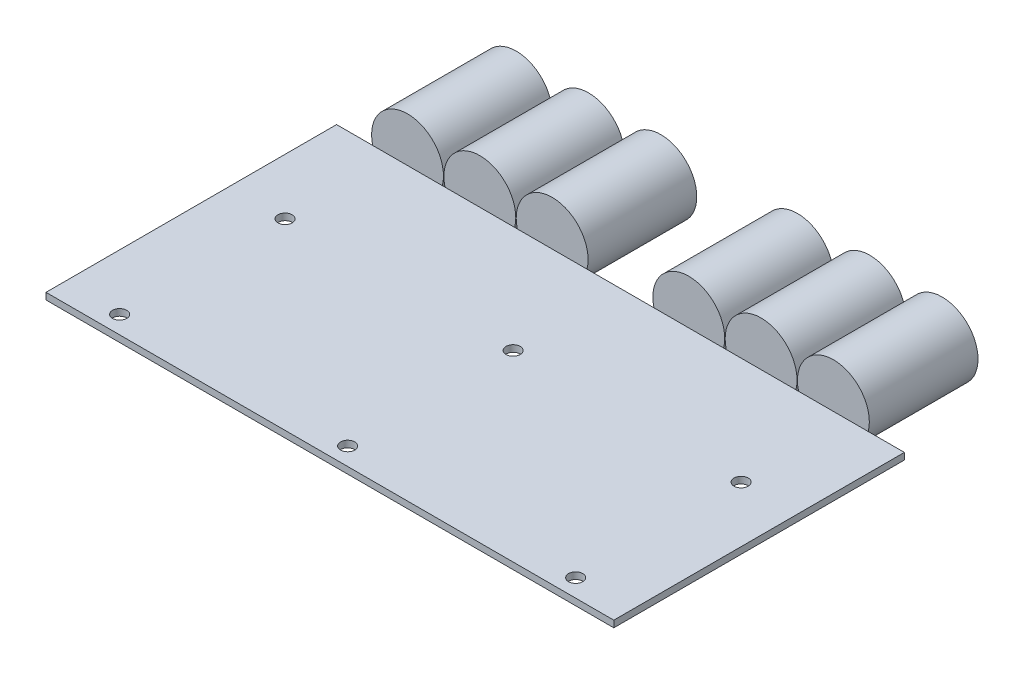
SolidWorks part; units mm, degrees
ref_plane "Front Plane" through (0, 0, 0) normal (0, 0, 1) x (1, 0, 0)
ref_plane "Top Plane" through (0, 0, 0) normal (0, 1, 0) x (1, 0, 0)
ref_plane "Right Plane" through (0, 0, 0) normal (1, 0, 0) x (0, 0, -1)
sketch "Sketch1" plane through (0, 0, 0) normal (0, 1, 0) x (1, 0, 0)
  line L1 (64, 32.75) -> (-64, 32.75)
  line L2 (64, 32.75) -> (64, -32.75)
  line L3 (64, -32.75) -> (-64, -32.75)
  line L4 (-64, 32.75) -> (-64, -32.75)
  line L5 (64, 32.75) -> (-64, -32.75) construction
  line L6 (64, -32.75) -> (-64, 32.75) construction
  point P0 (0, 0)
  dimension "D1" = 65.5
  dimension "D2" = 128
extrude "Boss-Extrude1" add sketch "Sketch1" along normal blind 1.5
sketch "Sketch2" plane through (0, 0, 0) normal (0, 1, 0) x (1, 0, 0)
  line L0 (0, 8.55) -> (0, -28.75) construction
  line L2 (-64, -32.75) -> (64, -32.75) construction
  line L3 (-64, 32.75) -> (-64, -32.75) construction
  circle A0 centre (-51.4, -28.75) radius 1.6
  circle A1 centre (0, -28.75) radius 1.6
  circle A2 centre (51.4, -28.75) radius 1.6
  circle A3 centre (-51.4, 8.55) radius 1.6
  circle A4 centre (0, 8.55) radius 1.6
  circle A5 centre (51.4, 8.55) radius 1.6
  point P12 (0, 0)
  point P13 (0, 9.9256)
  point P14 (0, 0)
  point P15 (0, -26.9408)
  point P16 (0, 0)
  point P17 (-0.5672, 8.0822)
  dimension "D1" = 3.2
  dimension "D2" = 2.4
  dimension "D4" = 48.2
  dimension "D5" = 34.1
  dimension "D3" = 11
extrude "Cut-Extrude2" cut sketch "Sketch2" along normal through all
sketch "Sketch3" plane through (0, 0, 0) normal (0, -1, 0) x (1, 0, 0)
  line L0 (-64, 32.75) -> (64, 32.75) construction
  line L1 (52.5, 1.75) -> (-52.5, 1.75)
  line L2 (52.5, 1.75) -> (52.5, 19.75)
  line L3 (52.5, 19.75) -> (-52.5, 19.75)
  line L4 (-52.5, 1.75) -> (-52.5, 19.75)
  line L5 (52.5, 1.75) -> (-52.5, 19.75) construction
  line L6 (52.5, 19.75) -> (-52.5, 1.75) construction
  point P0 (0, 10.75)
  point P5 (0, 0)
  dimension "D1" = 105
  dimension "D2" = 18
  dimension "D3" = 13
extrude "Boss-Extrude2" add sketch "Sketch3" along normal blind 1
sketch "Sketch4" plane through (0, 0, -32.75) normal (0, 0, -1) x (-1, 0, 0)
  line L0 (0, 0) -> (0, 1.5) construction
  line L1 (-64, 1.5) -> (64, 1.5) construction
  circle A0 centre (-48, 3.5) radius 8.1
  circle A1 centre (-31.7, 3.5) radius 8.1
  circle A2 centre (-15.4, 3.5) radius 8.1
  circle A3 centre (15.4, 3.5) radius 8.1
  circle A4 centre (31.7, 3.5) radius 8.1
  circle A5 centre (48, 3.5) radius 8.1
  point P17 (0, 0)
  point P18 (0, 0)
  point P19 (-49.0831, 3.5952)
  dimension "D1" = 16.2
  dimension "D2" = 2
  dimension "D3" = 48
  dimension "D4" = 16.3
  dimension "D5" = 16.3
extrude "Boss-Extrude4" add sketch "Sketch4" along normal offset from surface (24.5 mm away) 90 up to face at (0, 0.75, 32.75)
sketch "Sketch5" plane through (0, 0, 0) normal (0, -1, 0) x (1, 0, 0)
  line L0 (0, 0) -> (0, -32.75) construction
  line L1 (-60.8295, 25.8925) -> (-58.9862, 25.8925)
  line L2 (-60.8295, 25.8925) -> (-60.8295, 12.4221)
  line L3 (-60.8295, 12.4221) -> (-58.9862, 12.4221)
  line L4 (-58.9862, 25.8925) -> (-58.9862, 12.4221)
  line L5 (-62.8146, 10.8624) -> (-60.8295, 10.8624)
  line L6 (-62.8146, 10.8624) -> (-62.8146, -6.4365)
  line L7 (-62.8146, -6.4365) -> (-60.8295, -6.4365)
  line L8 (-60.8295, 10.8624) -> (-60.8295, -6.4365)
  line L9 (-44.25, -6.15) -> (-3.25, -6.15)
  line L10 (-44.25, -6.15) -> (-44.25, -23.15)
  line L11 (-44.25, -23.15) -> (-3.25, -23.15)
  line L12 (-3.25, -6.15) -> (-3.25, -23.15)
  line L17 (8.0952, -32.75) -> (-8.0952, -32.75) construction
  line L18 (3.25, -6.15) -> (3.25, -23.15)
  line L19 (44.25, -23.15) -> (3.25, -23.15)
  line L20 (44.25, -6.15) -> (44.25, -23.15)
  line L21 (44.25, -6.15) -> (3.25, -6.15)
  line L22 (60.8295, 10.8624) -> (60.8295, -6.4365)
  line L23 (62.8146, -6.4365) -> (60.8295, -6.4365)
  line L24 (62.8146, 10.8624) -> (62.8146, -6.4365)
  line L25 (62.8146, 10.8624) -> (60.8295, 10.8624)
  line L26 (58.9862, 25.8925) -> (58.9862, 12.4221)
  line L27 (60.8295, 12.4221) -> (58.9862, 12.4221)
  line L28 (60.8295, 25.8925) -> (60.8295, 12.4221)
  line L29 (60.8295, 25.8925) -> (58.9862, 25.8925)
  line L30 (-64, -30.15) -> (64, -30.15)
  line L31 (-64, -32.75) -> (-64, 32.75) construction
  line L32 (64, 32.75) -> (64, -32.75) construction
  line L34 (-44.25, -23.15) -> (-30.25, -23.15)
  line L35 (-44.25, -23.15) -> (-44.25, -26.65)
  line L36 (-44.25, -26.65) -> (-30.25, -26.65)
  line L37 (-30.25, -23.15) -> (-30.25, -26.65)
  line L38 (3.25, -23.15) -> (17.25, -23.15)
  line L39 (3.25, -23.15) -> (3.25, -26.65)
  line L40 (3.25, -26.65) -> (17.25, -26.65)
  line L41 (17.25, -23.15) -> (17.25, -26.65)
  line L42 (54.4533, 8.528) -> (57.4966, 8.528)
  line L43 (54.4533, 8.528) -> (54.4533, -0.6019)
  line L44 (54.4533, -0.6019) -> (57.4966, -0.6019)
  line L45 (57.4966, 8.528) -> (57.4966, -0.6019)
  point P45 (57.4966, -0.6019)
  point P46 (54.4533, 8.528)
  dimension "D1" = 9.6
  dimension "D2" = 41
  dimension "D3" = 6.5
  dimension "D4" = 17
  dimension "D5" = 7
  dimension "D6" = 14
  dimension "D7" = 3.5
sketch "Sketch6" plane through (0, 0, 0) normal (0, -1, 0) x (1, 0, 0)
  line L0 (-42, 32.75) -> (-42, 52.75) construction
  line L1 (-64, 32.75) -> (64, 32.75)
  line L2 (-64, 32.75) -> (-64, 52.75)
  line L3 (-64, 52.75) -> (64, 52.75)
  line L4 (64, 32.75) -> (64, 52.75)
  line L5 (-26, 32.75) -> (-26, 52.75) construction
  line L6 (-10, 52.75) -> (-10, 32.75) construction
  line L7 (0, 52.75) -> (0, 32.75) construction
  line L8 (10, 52.75) -> (10, 32.75) construction
  line L9 (26, 32.75) -> (26, 52.75) construction
  line L10 (42, 32.75) -> (42, 52.75) construction
  dimension "D1" = 20
  dimension "D2" = 22
  dimension "D3" = 16
  dimension "D4" = 16
equation "\"D4@Sketch4\"=\"D1@Sketch4\"+.1"
equation "\"D5@Sketch4\"=\"D4@Sketch4\""
